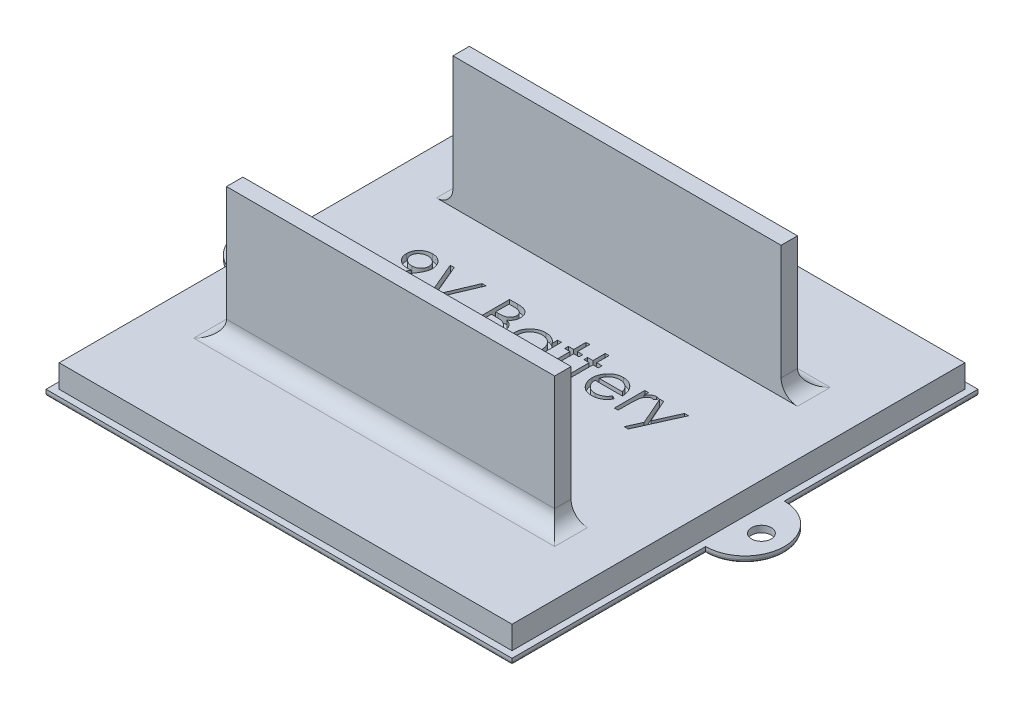
SolidWorks part; units mm, degrees
other "DetailItem2"
other "Markup1"
sketch "Sketch11" plane through (-41.5, 7, -35.5) normal (0, 1, 0) x (1, 0, 0)
sketch "Sketch12" plane through (-41.5, 7, -35.5) normal (0, 1, 0) x (1, 0, 0)
sketch "Sketch13" plane through (-41.5, 7, -35.5) normal (0, 1, 0) x (1, 0, 0)
sketch "Sketch15" plane through (-41.5, 7, -35.5) normal (0, 1, 0) x (1, 0, 0)
sketch "Sketch16" plane through (-41.5, 7, -35.5) normal (0, 1, 0) x (1, 0, 0)
sketch "Sketch17" plane through (-41.5, 7, -35.5) normal (0, 1, 0) x (1, 0, 0)
sketch "Sketch18" plane through (-41.5, 7, -35.5) normal (0, 1, 0) x (1, 0, 0)
sketch "Sketch19" plane through (-41.5, 7, -35.5) normal (0, 1, 0) x (1, 0, 0)
sketch "Sketch20" plane through (-41.5, 12, -35.5) normal (0, 1, 0) x (1, 0, 0)
sketch "Sketch21" plane through (-41.5, 25.5, -40.5) normal (0, 1, 0) x (1, 0, 0)
sketch "Sketch32" plane through (-41.5, 25.5, -40.5) normal (0, 1, 0) x (1, 0, 0)
sketch "Sketch36" plane through (-41.5, 25.5, -40.5) normal (0, 1, 0) x (1, 0, 0)
sketch "Sketch39" plane through (-41.5, 25.5, -40.5) normal (0, 1, 0) x (1, 0, 0)
sketch "Sketch42" plane through (-41.5, 25.5, -40.5) normal (0, 1, 0) x (1, 0, 0)
sketch "Sketch45" plane through (-41.5, 25.5, -35.5) normal (0, 1, 0) x (1, 0, 0)
sketch "Sketch55" plane through (-41.5, 25.5, -35.5) normal (0, 1, 0) x (1, 0, 0)
sketch "Sketch58" plane through (-41.5, 25.5, -35.5) normal (0, 1, 0) x (1, 0, 0)
other "Markup2"
sketch "Sketch37" plane through (41.5, 0.9701, -40.5) normal (1, 0, 0) x (0, 0, -1)
sketch "Sketch40" plane through (41.5, 0.9701, -40.5) normal (1, 0, 0) x (0, 0, -1)
sketch "Sketch43" plane through (41.5, 0.9701, -40.5) normal (1, 0, 0) x (0, 0, -1)
sketch "Sketch46" plane through (41.5, 0, -35.5) normal (1, 0, 0) x (0, 0, -1)
sketch "Sketch56" plane through (41.5, 0.9701, -35.5) normal (1, 0, 0) x (0, 0, -1)
sketch "Sketch59" plane through (41.5, 0.9701, -35.5) normal (1, 0, 0) x (0, 0, -1)
other "Markup3"
sketch "Sketch38" plane through (-41.5, 25.5, -40.5) normal (0, 1, 0) x (0, 0, -1)
sketch "Sketch41" plane through (-41.5, 25.5, -40.5) normal (0, 1, 0) x (0, 0, -1)
sketch "Sketch44" plane through (-41.5, 25.5, -40.5) normal (0, 1, 0) x (0, 0, -1)
sketch "Sketch47" plane through (-41.5, 25.5, -35.5) normal (0, 1, 0) x (0, 0, -1)
sketch "Sketch57" plane through (-41.5, 25.5, -35.5) normal (0, 1, 0) x (0, 0, -1)
sketch "Sketch60" plane through (-41.5, 25.5, -35.5) normal (0, 1, 0) x (0, 0, -1)
ref_plane "Front Plane" through (0, 0, 0) normal (0, 0, 1) x (1, 0, 0)
ref_plane "Top Plane" through (0, 0, 0) normal (0, 1, 0) x (1, 0, 0)
ref_plane "Right Plane" through (0, 0, 0) normal (1, 0, 0) x (0, 0, -1)
sketch "Sketch1" plane through (0, 0, 0) normal (0, 1, 0) x (1, 0, 0)
  line L1 (-35.5, -35.5) -> (35.5, -35.5)
  line L2 (-35.5, -35.5) -> (-35.5, 35.5)
  line L3 (-35.5, 35.5) -> (35.5, 35.5)
  line L4 (35.5, -35.5) -> (35.5, 35.5)
  line L5 (-35.5, -35.5) -> (35.5, 35.5) construction
  line L6 (-35.5, 35.5) -> (35.5, -35.5) construction
  point P0 (0, 0)
  dimension "D1" = 71
  dimension "D2" = 71
extrude "Boss-Extrude1" add sketch "Sketch1" along normal blind 4.5
sketch "text" plane through (0, 4.5, 0) normal (0, 1, 0) x (1, 0, 0)
  line L0 (-35.4043, 1.8177) -> (35.5957, 1.8177) construction
  text T0 "9V Battery \r\nHolder" font "Century Gothic" height in points 24
extrude "Cut-Extrude1" cut sketch "text" against normal blind 1
sketch "Sketch4" plane through (0, 4.5, 0) normal (0, 1, 0) x (1, 0, 0)
  line L0 (-35.5, 35.5) -> (-35.5, -35.5) construction
  line L1 (-35.5, 6) -> (-35.5, -6)
  arc A0 (-35.5, 6) -> (-35.5, -6) centre (-35.5, 0) ccw
  dimension "D1" = 6
extrude "Boss-Extrude3" add sketch "Sketch4" against normal up to surface (4.5 mm away) up to face at (0, 0, 0)
sketch "Sketch5" plane through (0, 4.5, 0) normal (0, 1, 0) x (1, 0, 0)
  line L0 (-35.5, 35.5) -> (-35.5, 6) construction
  circle A0 centre (-38, 0) radius 1.5
  dimension "D1" = 3
  dimension "D2" = 2.5
extrude "Cut-Extrude2" cut sketch "Sketch5" against normal up to surface (4.5 mm away) up to face at (-12.8333, 0, 0)
mirror "Mirror3" about plane through (0, 0, 0) normal (1, 0, 0) of "Boss-Extrude3", "Cut-Extrude2"
sketch "Sketch61" plane through (0, 4.5, 0) normal (0, 1, 0) x (1, 0, 0)
  line L0 (35.5, 6) -> (35.5, 35.5) construction
  line L1 (-34.5, -34.5) -> (34.5, -34.5)
  line L2 (-34.5, -34.5) -> (-34.5, 34.5)
  line L3 (-34.5, 34.5) -> (34.5, 34.5)
  line L4 (34.5, -34.5) -> (34.5, 34.5)
  line L5 (-34.5, -34.5) -> (34.5, 34.5) construction
  line L6 (-34.5, 34.5) -> (34.5, -34.5) construction
  line L7 (35.5, 35.5) -> (-35.5, 35.5) construction
  line L8 (-44.5, 44.5) -> (44.5, 44.5)
  line L9 (44.5, -44.5) -> (44.5, 44.5)
  line L10 (-44.5, -44.5) -> (44.5, -44.5)
  line L11 (-44.5, -44.5) -> (-44.5, 44.5)
  point P0 (0, 0)
  dimension "D1" = 1
  dimension "D2" = 1
  dimension "D3" = 10
extrude "Cut-Extrude21" cut sketch "Sketch61" against normal offset from surface (3.5 mm away) 1 up to face at (38, 0, -1.5)
sketch "Sketch9" plane through (0, 4.5, 0) normal (0, 1, 0) x (1, 0, 0)
  line L1 (-25, 18.5) -> (25, 18.5)
  line L2 (-25, 18.5) -> (-25, 16)
  line L3 (-25, 16) -> (25, 16)
  line L4 (25, 18.5) -> (25, 16)
  point P4 (0, 16)
  dimension "D1" = 50
  dimension "D2" = 2.5
  dimension "D3" = 16
extrude "top track" add sketch "Sketch9" along normal blind 20 contours L2 L1 L4 L3
fillet "Fillet1" radius 2.5 3 edges at (25, 4.5, -17.25) (0, 4.5, -18.5) (-25, 4.5, -17.25)
mirror "Mirror4" about plane through (0, 0, 0) normal (0, 0, 1) of "top track", "Fillet1"
fillet "Fillet2" radius 0.5 8 edges at (35.5, 0, 20.75) (41.5, 0, 0) (35.5, 0, -20.75) (0, 0, -35.5) (-35.5, 0, -20.75) (-41.5, 0, 0) (-35.5, 0, 20.75) (0, 0, 35.5)
equation "\"Screw_Diameter\"=3"
